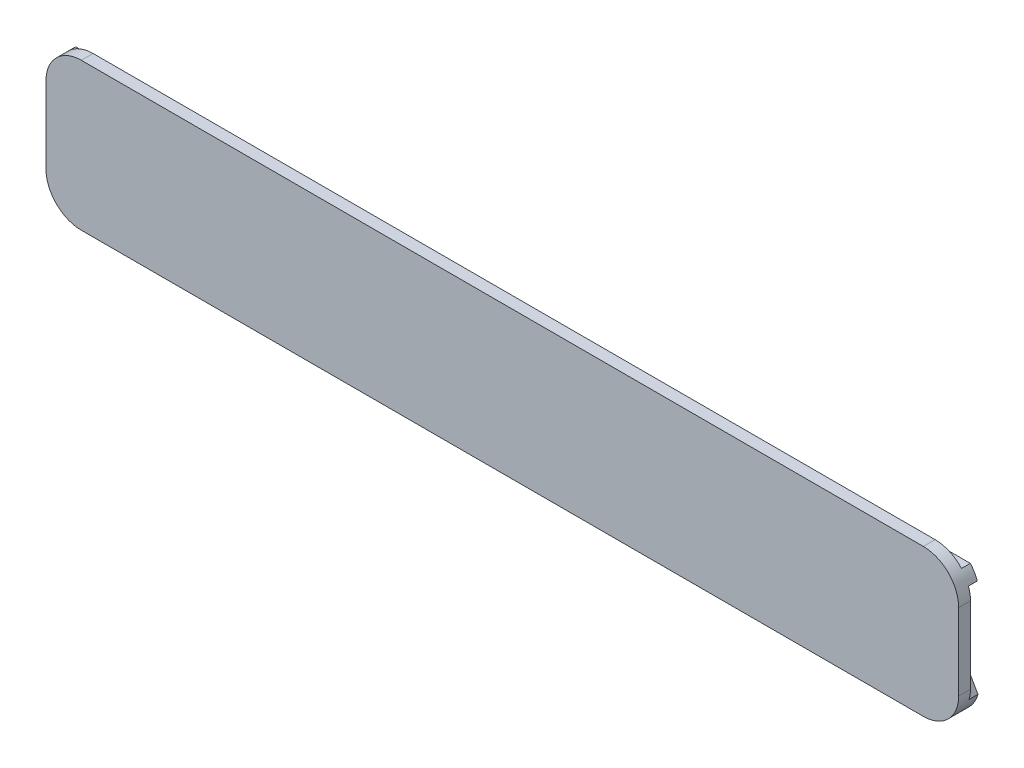
SolidWorks part; units mm, degrees
ref_plane "Front Plane" through (0, 0, 0) normal (0, 0, 1) x (1, 0, 0)
ref_plane "Top Plane" through (0, 0, 0) normal (0, 1, 0) x (1, 0, 0)
ref_plane "Right Plane" through (0, 0, 0) normal (1, 0, 0) x (0, 0, -1)
sketch "Sketch1" plane through (0, 0, 0) normal (0, 0, 1) x (1, 0, 0)
  line L0 (0, 0) -> (55.7, 0) construction
  line L1 (-49.65, 12.5) -> (105.35, 12.5)
  line L2 (-49.65, 12.5) -> (-49.65, -12.5)
  line L3 (-49.65, -12.5) -> (105.35, -12.5)
  line L4 (105.35, 12.5) -> (105.35, -12.5)
  circle A0 centre (55.7, 0) radius 3 construction
  circle A1 centre (0, 0) radius 3 construction
  circle A2 centre (55.7, 0) radius 3 construction
  circle A3 centre (0, 0) radius 3 construction
  circle A4 centre (0, 0) radius 3.2
  circle A5 centre (55.7, 0) radius 3.2
  point P14 (27.85, 0)
  point P15 (27.85, 12.5)
  point P16 (105.35, 0)
  dimension "D2" = 25
  dimension "D3" = 155
  dimension "D1" = 0.2
extrude "Boss-Extrude1" add sketch "Sketch1" against normal blind 1
sketch "Sketch2" plane through (0, 0, 0) normal (0, 0, 1) x (1, 0, 0)
  line L4 (-49.65, 12.5) -> (-49.65, -12.5)
  line L5 (-49.65, -12.5) -> (105.35, -12.5)
  line L6 (105.35, -12.5) -> (105.35, 12.5)
  line L7 (105.35, 12.5) -> (-49.65, 12.5)
  line L8 (-49.65, 12.5) -> (-49.65, -12.5)
  line L9 (-49.65, -12.5) -> (105.35, -12.5)
  line L10 (105.35, -12.5) -> (105.35, 12.5)
  line L11 (105.35, 12.5) -> (-49.65, 12.5)
  dimension "D1" = 0
extrude "Boss-Extrude2" add sketch "Sketch2" along normal blind 1
sketch "Sketch6" plane through (0, 0, -1) normal (0, 0, -1) x (-1, 0, 0)
  circle A0 centre (0, 0) radius 3.2 construction
  circle A1 centre (-55.7, 0) radius 3.2 construction
  circle A2 centre (0, 0) radius 3.2
  circle A3 centre (-55.7, 0) radius 3.2
  circle A4 centre (-55.7, 0) radius 5.2
  circle A5 centre (0, 0) radius 5.2
  dimension "D1" = 2
extrude "Boss-Extrude5" add sketch "Sketch6" along normal blind 2.5
sketch "Sketch5" plane through (0, 0, -1) normal (0, 0, -1) x (-1, 0, 0)
  line L0 (-105.35, 0) -> (49894.65, 0) construction
  line L1 (-105.35, -12.5) -> (-105.35, 12.5) construction
  line L2 (49.65, 12.5) -> (49.65, -12.5) construction
  line L3 (-27.85, -10.5) -> (-27.85, -8.5)
  line L4 (-105.35, 10.5) -> (-27.85, 10.5)
  line L5 (-105.35, 10.5) -> (-105.35, 8.5)
  line L6 (-105.35, 8.5) -> (-95.535, 8.5)
  line L7 (-27.85, 10.5) -> (-27.85, 8.5)
  line L8 (-103.0406, -8.5) -> (-81.4107, -8.5)
  line L9 (-105.35, -10.5) -> (-105.35, -8.5)
  line L10 (-105.35, -10.5) -> (-27.85, -10.5)
  line L11 (-105.35, 12.5) -> (49.65, 12.5) construction
  line L12 (-105.35, -8.5) -> (-95.535, 8.5)
  line L13 (-93.2256, 8.5) -> (-91.2256, 8.5)
  line L14 (-88.9162, 8.5) -> (-79.1013, -8.5)
  line L15 (-79.1013, -8.5) -> (-77.1013, -8.5)
  line L16 (-74.7919, -8.5) -> (-64.9769, 8.5)
  line L17 (-103.0406, -8.5) -> (-93.2256, 8.5)
  line L18 (-93.2256, 8.5) -> (-91.2256, 8.5)
  line L19 (-91.2256, 8.5) -> (-81.4107, -8.5)
  line L20 (-77.1013, -8.5) -> (-67.2863, 8.5)
  line L21 (-40.9744, 8.5) -> (-31.1594, -8.5)
  line L23 (-28.85, -8.5) -> (-38.665, 8.5)
  line L25 (-93.2256, 8.5) -> (-91.2256, 8.5)
  line L26 (-88.9162, 8.5) -> (-67.2863, 8.5)
  line L27 (-79.1013, -8.5) -> (-77.1013, -8.5)
  line L28 (-74.7919, -8.5) -> (-49.6, -8.5)
  line L29 (-64.9769, 8.5) -> (-45.0449, 8.5)
  line L30 (-38.665, 8.5) -> (-27.85, 8.5)
  line L31 (-28.85, -8.5) -> (-27.85, -8.5)
  line L32 (-45.0449, 8.5) -> (-49.6, -8.5)
  line L34 (-47.5295, -8.5) -> (-42.9744, 8.5)
  line L35 (-42.9744, 8.5) -> (-40.9744, 8.5)
  line L36 (-47.5295, -8.5) -> (-31.1594, -8.5)
  point P4 (-105.35, 0)
  point P7 (49.65, 0)
  point P34 (-27.85, 12.5)
  line M32 (-105.35, 12.5) -> (-105.35, -12.5)
  dimension "D1" = 2
  dimension "D2" = 2
  dimension "D3" = 2
  dimension "D4" = 2
  dimension "D5" = 2
  dimension "D6" = 2
  dimension "D7" = 60
  dimension "D8" = 2
  dimension "D9" = 1
  dimension "D10" = 2
  dimension "D11" = 45
extrude "Boss-Extrude4" add sketch "Sketch5" along normal blind 1.5 contours L12 L0 L17 L13 L19 L14 L26 L20 L16 L29 L21 L23 L30 L7 L4 L6 M32 | L0 L12 L10 L3 L31 L23 L21 L28 L16 L20 L15 L14 L19 L8 L17 M32 region at (66.9728, 7.4905, -1) region at (99.2878, -0.7821, -1)
ref_plane "Plane1" through (27.85, 0, 0) normal (1, 0, 0) x (0, 0, -1)
mirror "Mirror1" about plane through (27.85, 0, 0) normal (1, 0, 0) of "Boss-Extrude4"
fillet "Fillet1" radius 6 4 edges at (105.35, 12.5, 0) (105.35, -12.5, 0) (-49.65, -12.5, 0) (-49.65, 12.5, 0)
sketch "Sketch3" plane through (0, 0, 1) normal (0, 0, 1) x (1, 0, 0)
  line L0 (-49.65, -5) -> (105.35, -5) construction
  line L1 (-43.65, -12.5) -> (99.35, -12.5) construction
  line L2 (-49.65, 6.5) -> (-49.65, -6.5) construction
  text T0 "ED Robotics" font "Century Gothic" height 10
  point P7 (27.85, -12.5)
  point P8 (27.85, -5)
  dimension "D1" = 5
extrude "Engraved team name" [suppressed] cut sketch "Sketch3" against normal blind 0.5
equation "\"D3@Sketch5\"=\"D1@Sketch5\""
equation "\"D4@Sketch5\"=\"D3@Sketch5\""
equation "\"D5@Sketch5\"=\"D3@Sketch5\""
equation "\"D6@Sketch5\"=\"D3@Sketch5\""
equation "\"D8@Sketch5\"=\"D3@Sketch5\""
equation "\"D9@Sketch5\"=\"D3@Sketch5\"/2"
equation "\"D10@Sketch5\"=\"D3@Sketch5\""
